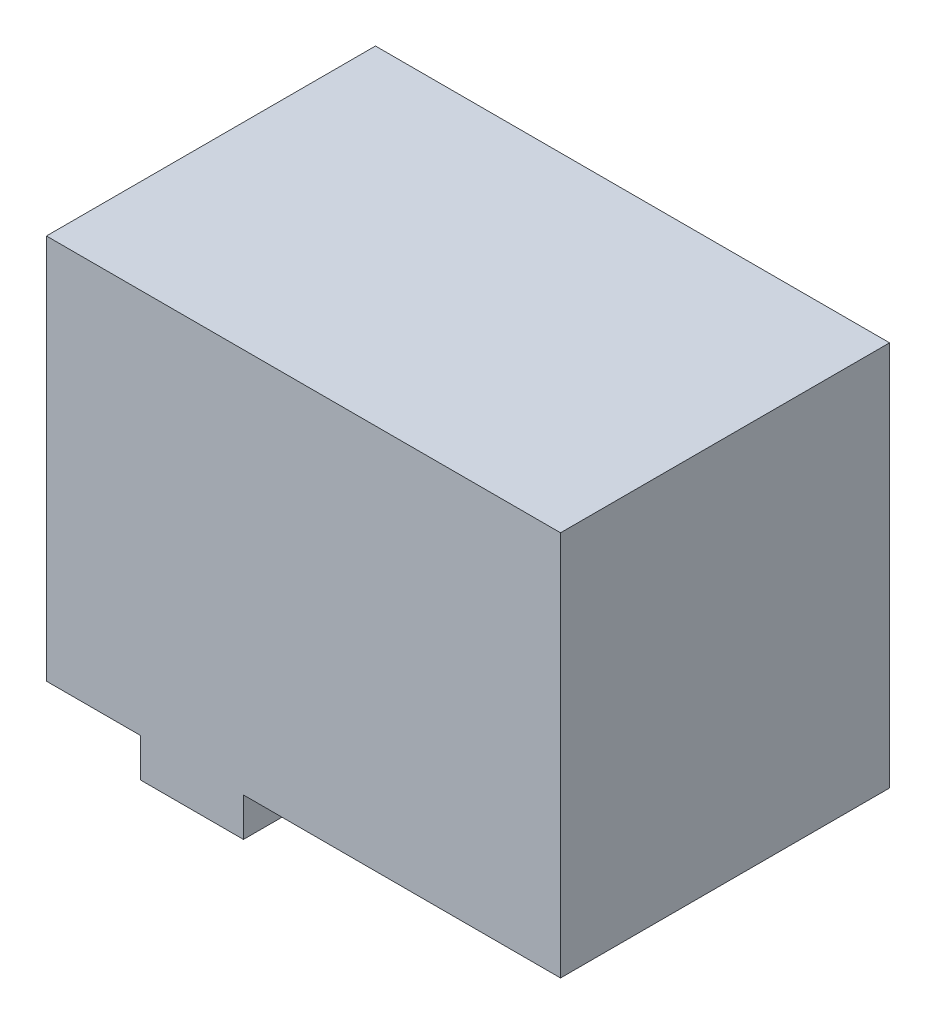
SolidWorks part; units mm, degrees
ref_plane "Front Plane" through (0, 0, 0) normal (0, 0, 1) x (1, 0, 0)
ref_plane "Top Plane" through (0, 0, 0) normal (0, 1, 0) x (1, 0, 0)
ref_plane "Right Plane" through (0, 0, 0) normal (1, 0, 0) x (0, 0, -1)
sketch "Sketch1" plane through (0, 0, 0) normal (0, 0, 1) x (1, 0, 0)
  line L11 (0, 0) -> (40, 0)
  line L12 (40, 0) -> (40, 15)
  line L16 (0, 15) -> (0, 0)
  line L18 (-8.3053, 94.5878) -> (165.7336, 94.5878) construction
  line L19 (-8.3053, 94.5878) -> (-8.3053, 14.5878) construction
  line L20 (-8.3053, 14.5878) -> (165.7336, 14.5878) construction
  line L21 (165.7336, 94.5878) -> (165.7336, 14.5878) construction
  line L22 (-8.3053, 94.5878) -> (165.7336, 14.5878) construction
  line L23 (-8.3053, 14.5878) -> (165.7336, 94.5878) construction
  line L24 (-36.6542, 15) -> (163.3458, 15)
  line L25 (-36.6542, 15) -> (-36.6542, 165)
  line L26 (-36.6542, 165) -> (163.3458, 165)
  line L27 (163.3458, 15) -> (163.3458, 165)
  line L28 (-36.6542, 15) -> (163.3458, 165) construction
  line L29 (-36.6542, 165) -> (163.3458, 15) construction
  point P7 (63.3458, 90)
  point P8 (0, 0)
  point P9 (0, 0)
  point P19 (78.7142, 54.5878)
  dimension "D1" = 40
  dimension "D2" = 15
  dimension "D3" = 200
  dimension "D4" = 80
  dimension "D5" = 174.039
  dimension "D6" = 150
extrude "Boss-Extrude1" add sketch "Sketch1" along normal blind 64 and the other way blind 64 contours L24 L27 L26 L25 | L24 L16 L11 L12 region at (20, 7.5, 0) region at (63.3458, 90, 0)
shell "Shell1" thickness 5 removed face at (20, 0, 0)
